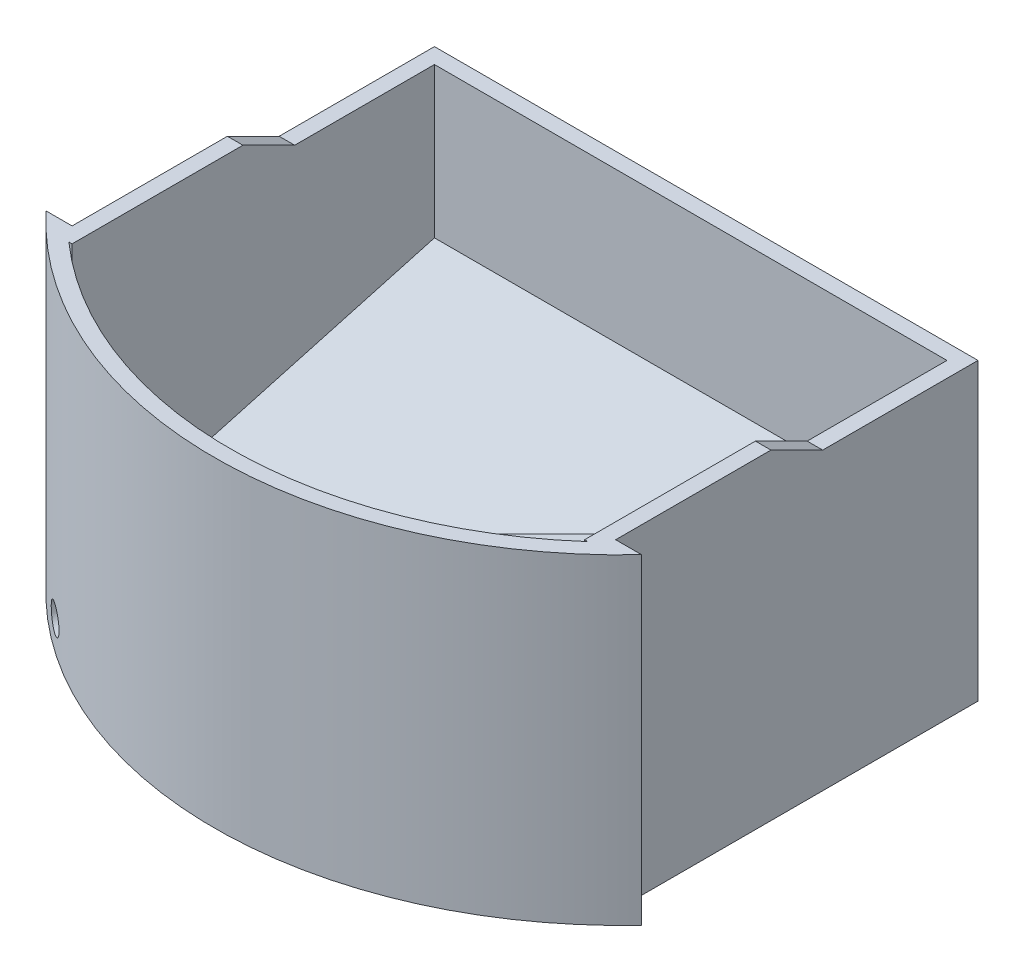
SolidWorks part; units mm, degrees
ref_plane "Front Plane" through (0, 0, 0) normal (0, 0, 1) x (1, 0, 0)
ref_plane "Top Plane" through (0, 0, 0) normal (0, 1, 0) x (1, 0, 0)
ref_plane "Right Plane" through (0, 0, 0) normal (1, 0, 0) x (0, 0, -1)
sketch "Sketch4" plane through (0, 0, 0) normal (0, 1, 0) x (1, 0, 0)
  line L0 (-6.35, 0) -> (139.7, 0)
  line L1 (0, 0) -> (133.35, 0)
  line L2 (0, 0) -> (0, 88.9)
  line L3 (0, 88.9) -> (133.35, 88.9)
  line L4 (133.35, 0) -> (133.35, 88.9)
  arc A1 (-6.35, 0) -> (139.7, 0) centre (66.675, 68.1037) ccw
  point P6 (66.675, -31.75)
  point P9 (66.675, 0)
  dimension "D1" = 133.35
  dimension "D2" = 88.9
  dimension "D3" = 146.05
  dimension "D4" = 6.35
  dimension "D5" = 31.75
extrude "Boss-Extrude2" add sketch "Sketch4" along normal blind 78.74 contours L0 A1 | L0 L4 L3 L2 region at (66.675, 0, 12.8907) region at (66.675, 0, -44.45)
sketch "Sketch5" plane through (0, 0, 0) normal (1, 0, 0) x (0, 0, -1)
  line L0 (0, 78.74) -> (88.9, 78.74) construction
  line L1 (0, 78.74) -> (88.9, 78.74)
  line L2 (88.9, 78.74) -> (88.9, 72.39)
  line L3 (88.9, 78.74) -> (88.9, 0) construction
  line L4 (88.9, 72.39) -> (50.8, 72.39)
  line L5 (50.8, 72.39) -> (38.1, 78.74)
  line L6 (38.1, 78.74) -> (88.9, 78.74)
  dimension "D1" = 12.7
  dimension "D2" = 38.1
  dimension "D3" = 6.35
extrude "Cut-Extrude4" cut sketch "Sketch5" along normal through all contours L2 L4 L5 L6
ref_plane "Plane1" through (3.81, 0, 0) normal (1, 0, 0) x (0, 0, -1)
ref_plane "Plane2" through (129.54, 0, 0) normal (1, 0, 0) x (0, 0, -1)
ref_plane "Plane3" through (0, 0, -85.09) normal (0, 0, -1) x (-1, 0, 0)
ref_plane "Plane4" through (0, 15.24, 0) normal (0, 1, 0) x (1, 0, 0)
ref_plane "Plane5" through (0, 0, 28.448) normal (0, 0, 1) x (1, 0, 0)
ref_plane "Plane6" through (15.24, 0, 0) normal (1, 0, 0) x (0, 0, -1)
ref_plane "Plane7" through (0, 0, -11.43) normal (0, 0, 1) x (1, 0, 0)
shell "Shell1" thickness 3.81 removed face at (66.675, 78.74, -7.4083) removed face at (66.675, 75.565, -44.45) removed face at (66.675, 72.39, -69.85)
sketch "Sketch8" plane through (0, 15.24, 0) normal (0, 1, 0) x (1, 0, 0)
  line L0 (0, 88.9) -> (133.35, 88.9) construction
  line L1 (133.35, 0) -> (133.35, 88.9) construction
  line L2 (-6.35, 0) -> (139.7, 0) construction
  line L3 (0, 0) -> (0, 88.9) construction
  line L4 (0, 88.9) -> (133.35, 88.9)
  line L5 (133.35, 0) -> (133.35, 88.9)
  line L6 (-6.35, 0) -> (139.7, 0)
  line L7 (0, 0) -> (0, 88.9)
  arc A0 (-6.35, 0) -> (139.7, 0) centre (66.675, 68.1037) ccw construction
  arc A1 (-6.35, 0) -> (139.7, 0) centre (66.675, 68.1037) ccw
extrude "fill in tube area" add sketch "Sketch8" against normal up to surface (15.24 mm away) contours L7 L6 L5 L4 | A1 L6 region at (66.675, 15.24, -44.45) up to plane "Top Plane"
sketch "Sketch7" plane through (3.81, 0, 0) normal (1, 0, 0) x (0, 0, -1)
  line L0 (-28.448, 78.74) -> (0, 15.24)
  line L1 (-28.448, 43.307) -> (-28.448, -43.307) construction
  line L2 (66.3575, 15.24) -> (-66.3575, 15.24) construction
  line L3 (0, 43.307) -> (0, -43.307) construction
  line L4 (0, 15.24) -> (-28.448, 15.24)
  line L5 (-28.448, 15.24) -> (-28.448, 78.74)
  line L6 (0, 78.74) -> (-31.75, 78.74) construction
  point P8 (0, 0)
extrude "Front inner slope" add sketch "Sketch7" along normal up to surface (125.73 mm away) up to plane "Plane2"
sketch "Sketch11" plane through (0, 15.24, 0) normal (0, 1, 0) x (1, 0, 0)
  line L0 (3.81, -43.307) -> (3.81, 43.307) construction
  line L1 (-6.35, 0) -> (139.7, 0) construction
  circle A0 centre (9.525, 5.715) radius 3.175
  dimension "D1" = 6.35
  dimension "D2" = 5.715
  dimension "D3" = 5.715
extrude "Cut-Extrude6" cut sketch "Sketch11" against normal blind 10.16
sketch "Sketch12" plane through (0, 0, -85.09) normal (0, 0, -1) x (-1, 0, 0)
  line L0 (-129.54, 35.56) -> (-15.24, 15.24)
  line L1 (-129.54, 43.307) -> (-129.54, -43.307) construction
  line L2 (-15.24, 43.307) -> (-15.24, -43.307) construction
  line L3 (66.3575, 15.24) -> (-66.3575, 15.24) construction
  line L4 (-15.24, 15.24) -> (-129.54, 15.24)
  line L5 (-129.54, 15.24) -> (-129.54, 35.56)
  dimension "D1" = 20.32
extrude "Inner Slope 1" add sketch "Sketch12" against normal up to surface (113.538 mm away) up to plane "Plane5"
sketch "Sketch9" plane through (0, 15.24, 0) normal (0, 1, 0) x (1, 0, 0)
  line L2 (-6.35, 0) -> (-6.35, -28.448)
  line L3 (-43.307, -28.448) -> (43.307, -28.448) construction
  line L4 (-6.35, -28.448) -> (41.2087, -28.448)
  line L5 (139.7, -28.448) -> (139.7, 0)
  line L6 (92.1413, -28.448) -> (139.7, -28.448)
  arc A0 (-6.35, 0) -> (139.7, 0) centre (66.675, 68.1037) ccw construction
  arc A1 (-6.35, 0) -> (41.2087, -28.448) centre (66.675, 68.1037) ccw
  arc A2 (92.1413, -28.448) -> (139.7, 0) centre (66.675, 68.1037) ccw
extrude "Remove extra inner slope material" cut sketch "Sketch9" along normal through all
sketch "Sketch13" plane through (3.81, 0, 0) normal (1, 0, 0) x (0, 0, -1)
  line L0 (85.09, 35.56) -> (11.43, 15.24)
  line L1 (85.09, -39.8145) -> (85.09, 39.8145) construction
  line L2 (11.43, 43.307) -> (11.43, -43.307) construction
  line L3 (66.3575, 15.24) -> (-66.3575, 15.24) construction
  line L4 (11.43, 15.24) -> (85.09, 15.24)
  line L5 (85.09, 15.24) -> (85.09, 35.56)
  dimension "D1" = 20.32
extrude "Inner Slope 2" add sketch "Sketch13" along normal up to surface (125.73 mm away) up to plane "Plane2"
sketch "Sketch14" plane through (0, 0, 0) normal (0, 0, 1) x (1, 0, 0)
  line L0 (0, -43.307) -> (0, 43.307) construction
  line L1 (66.3575, 15.24) -> (-66.3575, 15.24) construction
  circle A0 centre (9.525, 6.985) radius 3.175
  dimension "D3" = 6.35
  dimension "D1" = 9.525
  dimension "D2" = 8.255
extrude "Cut-Extrude7" cut sketch "Sketch14" against normal blind 8.89 and the other way through all
